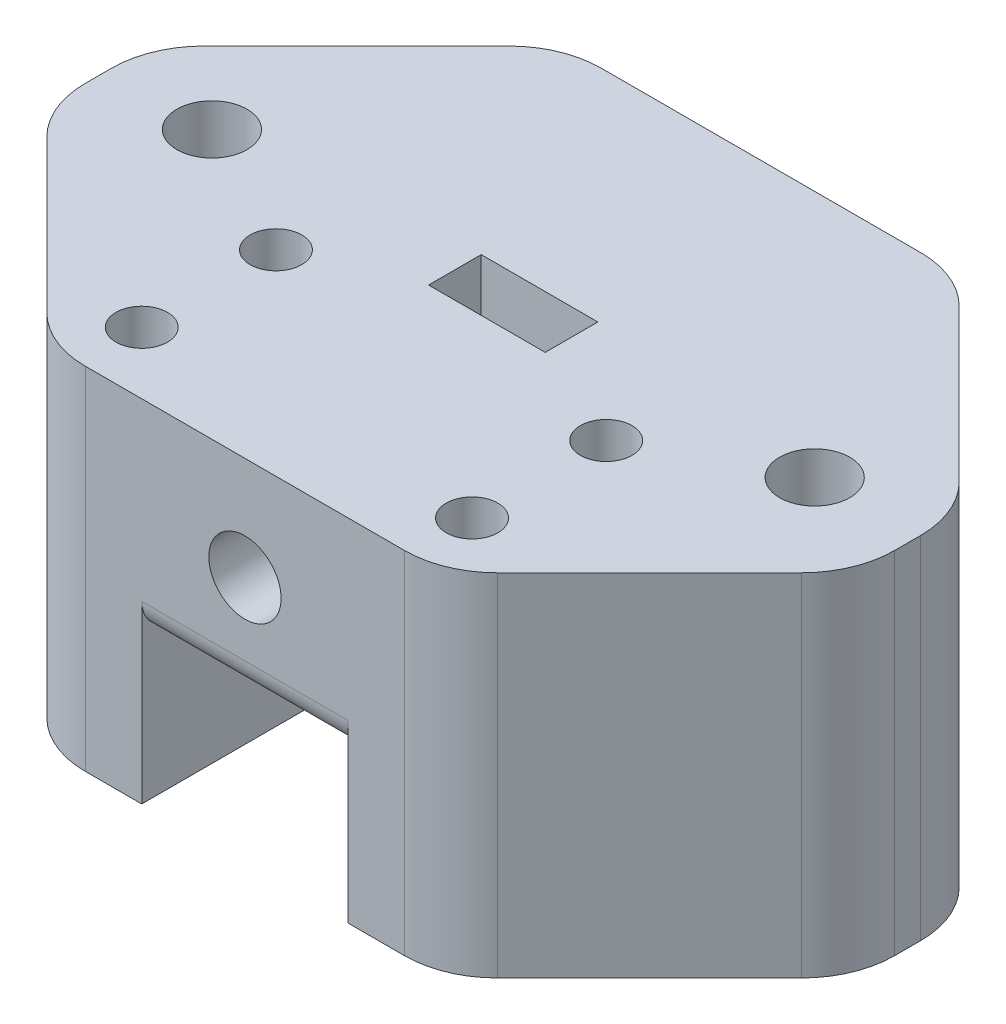
SolidWorks part; units mm, degrees
material "ABS PC"
ref_plane "Front Plane" through (0, 0, 0) normal (0, 0, 1) x (1, 0, 0)
ref_plane "Top Plane" through (0, 0, 0) normal (0, 1, 0) x (1, 0, 0)
ref_plane "Right Plane" through (0, 0, 0) normal (1, 0, 0) x (0, 0, -1)
sketch "Sketch1" plane through (0, 0, 0) normal (0, 1, 0) x (1, 0, 0)
  line L0 (0, 0) -> (0, 25)
  line L1 (0, 0) -> (39.2, 0)
  line L2 (0, 25) -> (39.2, 25)
  line L3 (39.2, 0) -> (39.2, 25)
  dimension "D1" = 39.2
  dimension "D2" = 25
extrude "Boss-Extrude1" add sketch "Sketch1" along normal blind 10
hole_wizard "Ø3.5 (3.5) Diameter Hole1" positions "Sketch8" profile "Sketch7" hole size "Ø3.5" standard "ANSI Metric" end condition through all
sketch "Sketch8" plane through (0, 0, -25) normal (0, 0, -1) x (-1, 0, 0)
  line L2 (0, 10) -> (0, 0) construction
  line L3 (-39.2, 0) -> (0, 0) construction
  point P0 (-19.6, 5)
  point P15 (-19.6, 0)
  dimension "D1" = 19.6
  dimension "D2" = 5
sketch "Sketch7" plane through (19.6, 5, -25) normal (1, 0, 0) x (0, 1, 0)
  line L0 (0, 0) -> (0, 25)
  line L1 (0, 25) -> (1.75, 25)
  line L2 (1.75, 25) -> (1.75, 0)
  line L5 (1.75, 0) -> (0, 0)
  line L11 (0, -6.35) -> (0, 107.95) construction
  dimension "Thru Hole Dia." = 3.5
  dimension "Thru Hole Depth" = 25
sketch "Sketch9" plane through (0, 0, 0) normal (0, -1, 0) x (1, 0, 0)
  line L0 (39.2, -25) -> (39.2, 0)
  line L1 (39.2, -25) -> (24.6, -25)
  line L2 (39.2, 0) -> (24.6, 0)
  line L3 (24.6, -25) -> (24.6, 0)
  line L4 (0, -25) -> (0, 0)
  line L5 (0, -25) -> (14.6, -25)
  line L6 (0, 0) -> (14.6, 0)
  line L7 (14.6, -25) -> (14.6, 0)
  dimension "D1" = 10
  dimension "D2" = 14.6
extrude "Boss-Extrude2" add sketch "Sketch9" along normal blind 7
sketch "Sketch10" plane through (0, 10, 0) normal (0, 1, 0) x (1, 0, 0)
  line L0 (16.775, 11.72) -> (22.425, 11.72)
  line L1 (16.775, 11.72) -> (16.775, 14.27)
  line L2 (22.425, 11.72) -> (22.425, 14.27)
  line L3 (16.775, 14.27) -> (22.425, 14.27)
  line L4 (0, 25) -> (0, 0) construction
  line L5 (39.2, 25) -> (0, 25) construction
  dimension "D1" = 5.65
  dimension "D2" = 2.55
  dimension "D3" = 16.775
  dimension "D4" = 10.73
extrude "Cut-Extrude4" cut sketch "Sketch10" against normal blind 10
hole_wizard "Ø2.5 (2.5) Diameter Hole1" positions "Sketch12" profile "Sketch11" hole size "Ø2.5" standard "ANSI Metric"
sketch "Sketch12" plane through (0, 10, 0) normal (0, 1, 0) x (1, 0, 0)
  line L0 (0, 0) -> (39.2, 0) construction
  line L1 (39.2, 0) -> (39.2, 25) construction
  point P0 (11.6, 3)
  point P2 (27.6, 3)
  point P4 (27.6, 9.5)
  point P6 (11.6, 9.5)
  dimension "D1" = 3
  dimension "D2" = 6.5
  dimension "D3" = 16
  dimension "D4" = 11.6
sketch "Sketch11" plane through (11.6, 10, -3) normal (1, 0, 0) x (0, 0, 1)
  line L0 (0, 0) -> (0, 7.7511)
  line L1 (0, 7.7511) -> (1.25, 7)
  line L2 (1.25, 7) -> (1.25, 0)
  line L5 (1.25, 0) -> (0, 0)
  line L10 (0, 7.7511) -> (-1.25, 7) construction
  line L11 (0, -6.35) -> (0, 107.95) construction
  dimension "Hole Dia." = 2.5
  dimension "Hole Depth" = 7
  dimension "Drill Angle" = 118
hole_wizard "Ø3.4 (3.4) Diameter Hole1" positions "Sketch3" profile "Sketch2" hole size "Ø3.4" standard "ANSI Metric" end condition through all
sketch "Sketch3" plane through (0, 10, 0) normal (0, 1, 0) x (1, 0, 0)
  line L0 (0, 25) -> (0, 0) construction
  line L1 (39.2, 0) -> (39.2, 25) construction
  line L3 (39.2, 25) -> (0, 25) construction
  point P0 (34.2, 13)
  point P2 (5, 13)
  dimension "D1" = 5
  dimension "D2" = 5
  dimension "D4" = 12
sketch "Sketch2" plane through (34.2, 10, -13) normal (1, 0, 0) x (0, 0, 1)
  line L0 (0, 0) -> (0, 17)
  line L1 (0, 17) -> (1.7, 17)
  line L2 (1.7, 17) -> (1.7, 0)
  line L5 (1.7, 0) -> (0, 0)
  line L11 (0, -6.35) -> (0, 107.95) construction
  dimension "Thru Hole Dia." = 3.4
  dimension "Thru Hole Depth" = 17
chamfer "Chamfer1" distance 10 angle 45 4 edges at (0, 1.5, -25) (0, 1.5, 0) (39.2, 1.5, 0) (39.2, 1.5, -25)
fillet "Fillet5" radius 4.5 8 edges at (29.2, 1.5, 0) (10, 1.5, 0) (0, 1.5, -10) (0, 1.5, -15) (10, 1.5, -25) (29.2, 1.5, -25) (39.2, 1.5, -10) (39.2, 1.5, -15)
fillet "Fillet6" radius 1.5 1 edges
hole_wizard "Ø3.4 (3.4) Diameter Hole2" positions "Sketch14" profile "Sketch13" hole size "Ø3.4" standard "ANSI Metric"
sketch "Sketch14" plane through (0, -7, 0) normal (0, -1, 0) x (-1, 0, 0)
  line L1 (-24.6, 25) -> (-27.336, 25) construction
  circle A1 centre (-34.2, 13) radius 1.7 construction
  circle A2 centre (-5, 13) radius 1.7 construction
  point P0 (-9.6, 13)
  point P2 (-29.6, 13)
  dimension "D3" = 4.6
  dimension "D1" = 12
  dimension "D2" = 4.6
sketch "Sketch13" plane through (9.6, -7, -13) normal (1, 0, 0) x (0, 0, -1)
  line L0 (0, 0) -> (0, 5.0215)
  line L1 (0, 5.0215) -> (1.7, 4)
  line L2 (1.7, 4) -> (1.7, 0)
  line L5 (1.7, 0) -> (0, 0)
  line L10 (0, 5.0215) -> (-1.7, 4) construction
  line L11 (0, -6.35) -> (0, 107.95) construction
  dimension "Hole Dia." = 3.4
  dimension "Hole Depth" = 4
  dimension "Drill Angle" = 118
